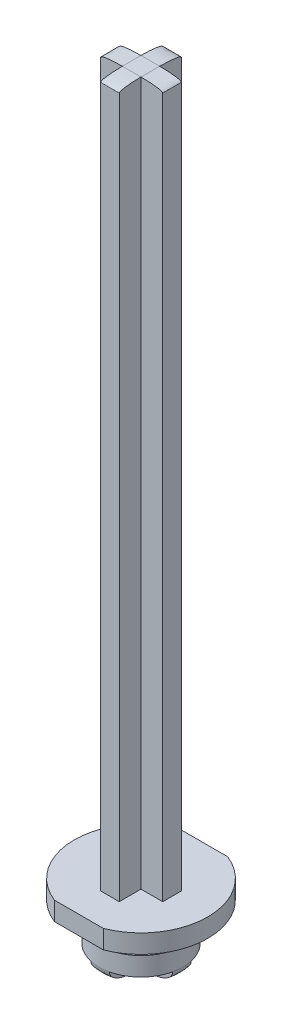
SolidWorks part; units mm, degrees
ref_plane "Front Plane" through (0, 0, 0) normal (0, 0, 1) x (1, 0, 0)
ref_plane "Top Plane" through (0, 0, 0) normal (0, 1, 0) x (1, 0, 0)
ref_plane "Right Plane" through (0, 0, 0) normal (1, 0, 0) x (0, 0, -1)
sketch "Sketch1" plane through (0, 0, 0) normal (0, 1, 0) x (1, 0, 0)
  circle A0 centre (0, 0) radius 4.3
  dimension "D1" = 8.6
extrude "Boss-Extrude1" add sketch "Sketch1" along normal blind 1.2
sketch "Sketch2" plane through (0, 1.2, 0) normal (0, 1, 0) x (1, 0, 0)
  line L1 (2, -0.6) -> (-2, -0.6)
  line L2 (2, -0.6) -> (2, 0.6)
  line L3 (2, 0.6) -> (-2, 0.6)
  line L4 (-2, -0.6) -> (-2, 0.6)
  line L5 (2, -0.6) -> (-2, 0.6) construction
  line L6 (2, 0.6) -> (-2, -0.6) construction
  line L7 (0.6, -2) -> (-0.6, -2)
  line L8 (0.6, -2) -> (0.6, 2)
  line L9 (0.6, 2) -> (-0.6, 2)
  line L10 (-0.6, -2) -> (-0.6, 2)
  line L11 (0.6, -2) -> (-0.6, 2) construction
  line L12 (0.6, 2) -> (-0.6, -2) construction
  point P0 (0, 0)
  point P6 (0, 0)
  dimension "D1" = 4
  dimension "D2" = 1.2
extrude "Boss-Extrude2" add sketch "Sketch2" along normal blind 45.3 contours L1 L4 L3 L2 | L8 L9 L10 L7
sketch "Sketch3" plane through (0, 0, 0) normal (0, -1, 0) x (1, 0, 0)
  line L1 (2, -0.6) -> (-2, -0.6)
  line L2 (2, -0.6) -> (2, 0.6)
  line L3 (2, 0.6) -> (-2, 0.6)
  line L4 (-2, -0.6) -> (-2, 0.6)
  line L5 (2, -0.6) -> (-2, 0.6) construction
  line L6 (2, 0.6) -> (-2, -0.6) construction
  line L7 (0.6, 2) -> (-0.6, 2)
  line L8 (0.6, 2) -> (0.6, -2)
  line L9 (0.6, -2) -> (-0.6, -2)
  line L10 (-0.6, 2) -> (-0.6, -2)
  line L11 (0.6, 2) -> (-0.6, -2) construction
  line L12 (0.6, -2) -> (-0.6, 2) construction
  point P0 (0, 0)
  point P6 (0, 0)
  dimension "D1" = 4
  dimension "D2" = 1.2
extrude "Boss-Extrude3" add sketch "Sketch3" along normal blind 1.2 contours L10 L9 L8 L7 | L1 L4 L3 L2
sketch "Sketch4" plane through (0, -1.2, 0) normal (0, -1, 0) x (1, 0, 0)
  circle A0 centre (0, 0) radius 2.7
  dimension "D1" = 5.4
extrude "Boss-Extrude4" add sketch "Sketch4" along normal blind 1.2
sketch "Sketch5" plane through (0, -2.4, 0) normal (0, -1, 0) x (1, 0, 0)
  line L1 (0.6, -2.7) -> (-0.6, -2.7)
  line L2 (0.6, -2.7) -> (0.6, 2.7)
  line L3 (0.6, 2.7) -> (-0.6, 2.7)
  line L4 (-0.6, -2.7) -> (-0.6, 2.7)
  line L5 (0.6, -2.7) -> (-0.6, 2.7) construction
  line L6 (0.6, 2.7) -> (-0.6, -2.7) construction
  line L7 (2.7, -0.6) -> (-2.7, -0.6)
  line L8 (2.7, -0.6) -> (2.7, 0.6)
  line L9 (2.7, 0.6) -> (-2.7, 0.6)
  line L10 (-2.7, -0.6) -> (-2.7, 0.6)
  line L11 (2.7, -0.6) -> (-2.7, 0.6) construction
  line L12 (2.7, 0.6) -> (-2.7, -0.6) construction
  circle A0 centre (0, 0) radius 2.7 construction
  point P0 (0, 0)
  point P6 (0, 0)
  point P11 (-2, -0.6)
  point P12 (-2, -0.6)
  point P13 (-2.2683, -0.6)
  circle M9 centre (0, 0) radius 2.7
  dimension "D1" = 1.2
extrude "Boss-Extrude5" add sketch "Sketch5" along normal blind 0.8 contours L9 L2 L7 M9 | L9 L2 L4 M9 | L4 L9 L7 M9 | L2 L7 L4 M9 | L2 L9 L4 L7
fillet "Fillet2" radius 1.4 4 edges at (-2, 46.5, 0) (0, 46.5, 2) (0, 46.5, -2) (2, 46.5, 0)
fillet "Fillet3" radius 1.5 4 edges at (0, -3.2, -2.7) (0, -3.2, 2.7) (-2.7, -3.2, 0) (2.7, -3.2, 0)
sketch "Sketch7" plane through (0, 0, 0) normal (0, -1, 0) x (1, 0, 0)
  line L1 (7, -4) -> (-7, -4) construction
  line L2 (7, -4) -> (7, 4) construction
  line L3 (7, 4) -> (-7, 4) construction
  line L4 (-7, -4) -> (-7, 4) construction
  line L5 (7, -4) -> (-7, 4) construction
  line L6 (7, 4) -> (-7, -4) construction
  line L7 (-7, 4) -> (7, 4)
  line L8 (-7, 4) -> (-7, 5)
  line L9 (-7, 5) -> (7, 5)
  line L10 (7, 4) -> (7, 5)
  line L11 (7, -4) -> (-7, -4)
  line L12 (7, -4) -> (7, -5)
  line L13 (7, -5) -> (-7, -5)
  line L14 (-7, -4) -> (-7, -5)
  point P0 (0, 0)
  dimension "D1" = 8
  dimension "D2" = 14
  dimension "D3" = 1
extrude "Cut-Extrude1" cut sketch "Sketch7" against normal blind 1.2
